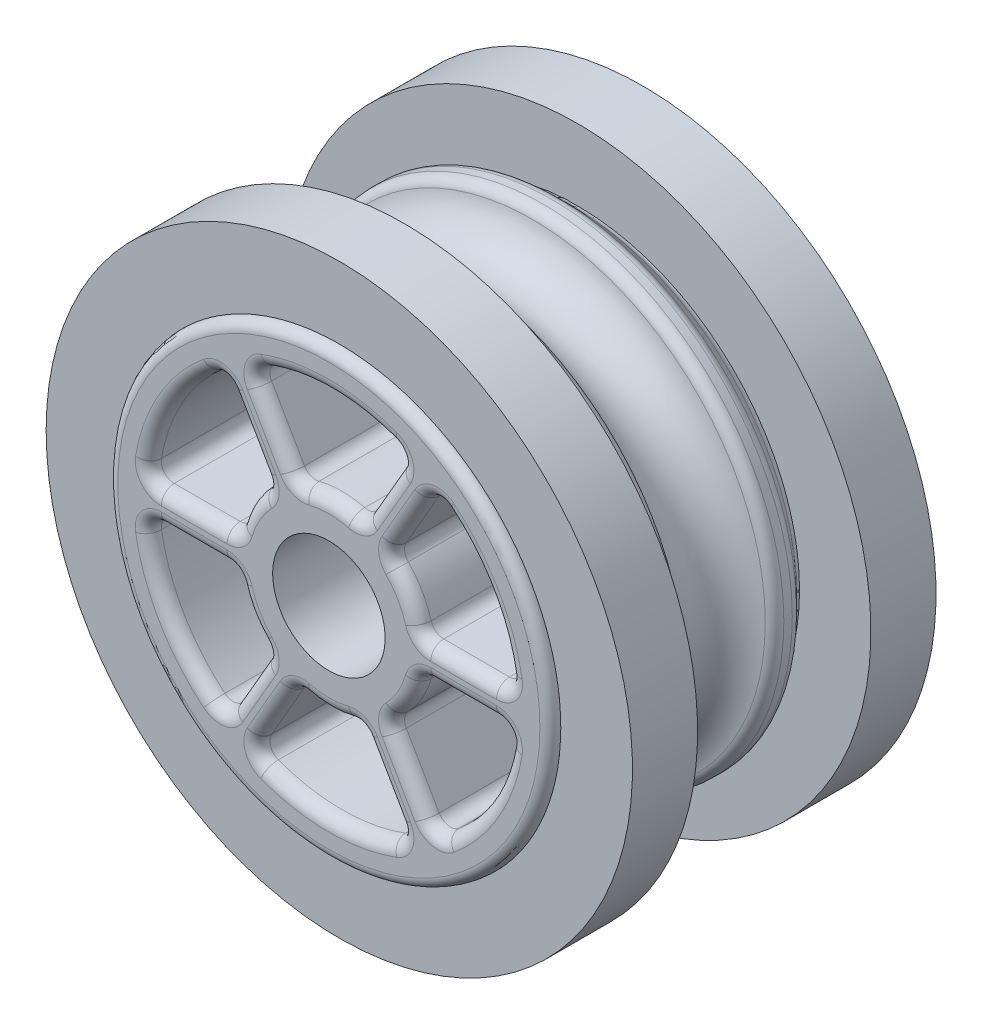
SolidWorks part; units mm, degrees
material "ABS"
ref_plane "Front Plane" through (0, 0, 0) normal (0, 0, 1) x (1, 0, 0)
ref_plane "Top Plane" through (0, 0, 0) normal (0, 1, 0) x (1, 0, 0)
ref_plane "Right Plane" through (0, 0, 0) normal (1, 0, 0) x (0, 0, -1)
sketch "Sketch1" plane through (0, 0, 0) normal (1, 0, 0) x (0, 0, -1)
  line L0 (-12.45, 4.318) -> (12.45, 4.318)
  line L1 (12.45, 4.318) -> (12.45, 17)
  line L2 (12.45, 17) -> (4.45, 17)
  line L3 (4.45, 17) -> (4.45, 18.5)
  line L4 (4.45, 18.5) -> (3.25, 18.5)
  line L5 (-3.25, 18.5) -> (-4.45, 18.5)
  line L6 (-4.45, 18.5) -> (-4.45, 17)
  line L7 (-4.45, 17) -> (-12.45, 17)
  line L8 (-12.45, 17) -> (-12.45, 4.318)
  line L9 (0, 0) -> (-26.6908, 0) construction
  arc A0 (3.25, 18.5) -> (-3.25, 18.5) centre (0, 18.5) cw
  point P0 (0, 4.318)
  point P12 (0, 0)
  point P13 (-14.9607, 4.318)
  point P15 (-26.6908, 0)
  point P19 (-14.45, 4.318)
  point P20 (0, 0)
  point P21 (0, 0)
  point P22 (-14.45, 4.318)
  dimension "D1" = 4.318
  dimension "D4" = 18.5
  dimension "D2" = 8
  dimension "D3" = 17
  dimension "D5" = 1.2
  dimension "D6" = 6.5
revolve "Revolve1" add sketch "Sketch1" angle 360 about L9
chamfer "Chamfer1" distance 2 angle 45 2 edges at (-17, 0, -4.45) (-17, 0, 4.45)
sketch "Sketch2" plane through (0, 0, 12.45) normal (0, 0, 1) x (1, 0, 0)
  line L0 (0, 0) -> (-7.625, 13.2069) construction
  line L1 (0, 0) -> (7.625, 13.2069) construction
  line L2 (-2.4688, 6.6761) -> (-5.9601, 12.7232)
  line L3 (2.4688, 6.6761) -> (5.9601, 12.7232)
  line L4 (0, 2.4) -> (-5.9601, 12.7232) construction
  line L5 (0, 2.4) -> (5.9601, 12.7232) construction
  arc A0 (-7.625, 13.2069) -> (7.625, 13.2069) centre (0, 0) cw construction
  circle A1 centre (0, 0) radius 15.25 construction
  arc A2 (-5.9601, 12.7232) -> (5.9601, 12.7232) centre (0, 0) cw
  arc A6 (2.4688, 6.6761) -> (-2.4688, 6.6761) centre (0, 0) ccw
  dimension "D1" = 60
  dimension "D2" = 1.2
extrude "Cut-Extrude1" cut sketch "Sketch2" against normal through all
pattern_circular "CirPattern1" count 6 over 360 about axis through (0, 0, 0) along (0, 0, -1) of "Cut-Extrude1"
fillet "Fillet2" radius 0.8 6 edges at (-17, 0, -6.45) (18.5, 0, -4.95) (-18.5, 0, -3.25) (-18.5, 0, 3.25) (-18.5, 0, 4.95) (17, 0, 6.45)
fillet "Fillet4" radius 0.8 2 edges at (-17, 0, -12.45) (-17, 0, 12.45)
fillet "Fillet5" radius 1 72 edges at (-4.2145, -9.6997, 12.45) (4.2145, -9.6997, 12.45) (6.2929, -8.4997, 12.45) (10.5074, -1.2, 12.45) (10.5074, 1.2, 12.45) (6.2929, 8.4997, 12.45) (4.2145, 9.6997, 12.45) (-4.2145, 9.6997, 12.45) (-6.2929, 8.4997, 12.45) (-10.5074, 1.2, 12.45) (-10.5074, -1.2, 12.45) (-6.2929, -8.4997, 12.45) (6.2929, 8.4997, -12.45) (10.5074, 1.2, -12.45) (10.5074, -1.2, -12.45) (6.2929, -8.4997, -12.45) (4.2145, -9.6997, -12.45) (-4.2145, -9.6997, -12.45) (-6.2929, -8.4997, -12.45) (-10.5074, -1.2, -12.45) (-10.5074, 1.2, -12.45) (-6.2929, 8.4997, -12.45) (-4.2145, 9.6997, -12.45) (4.2145, 9.6997, -12.45) (-5.9601, -12.7232, 0) (0, -14.05, -12.45) (5.9601, -12.7232, 0) (0, -14.05, 12.45) (8.0386, -11.5232, 0) (12.1677, -7.025, -12.45) (13.9987, -1.2, 0) (12.1677, -7.025, 12.45) (13.9987, 1.2, 0) (12.1677, 7.025, -12.45) (8.0386, 11.5232, 0) (12.1677, 7.025, 12.45) (5.9601, 12.7232, 0) (0, 14.05, -12.45) (-5.9601, 12.7232, 0) (0, 14.05, 12.45) (-8.0386, 11.5232, 0) (-12.1677, 7.025, -12.45) (-13.9987, 1.2, 0) (-12.1677, 7.025, 12.45) (-13.9987, -1.2, 0) (-12.1677, -7.025, -12.45) (-8.0386, -11.5232, 0) (-12.1677, -7.025, 12.45) (4.5473, 5.4761, 0) (7.0161, 1.2, 0) (-2.4688, 6.6761, 0) (2.4688, 6.6761, 0) (6.1644, 3.559, -12.45) (6.1644, 3.559, 12.45) (0, 7.118, -12.45) (0, 7.118, 12.45) (-7.0161, 1.2, 0) (-6.1644, 3.559, -12.45) (-4.5473, 5.4761, 0) (-6.1644, 3.559, 12.45) (-4.5473, -5.4761, 0) (-6.1644, -3.559, -12.45) (-7.0161, -1.2, 0) (-6.1644, -3.559, 12.45) (2.4688, -6.6761, 0) (0, -7.118, -12.45) (-2.4688, -6.6761, 0) (0, -7.118, 12.45) (7.0161, -1.2, 0) (6.1644, -3.559, -12.45) (4.5473, -5.4761, 0) (6.1644, -3.559, 12.45)
sketch "Sketch3" plane through (0, 0, 0) normal (1, 0, 0) x (0, 0, -1)
  line L0 (-6.7814, 17) -> (-11.65, 17) construction
  line L1 (-11.65, 17) -> (-6.65, 17)
  line L2 (-11.65, 17) -> (-11.65, 22.5)
  line L3 (-11.65, 22.5) -> (-6.65, 22.5)
  line L4 (-6.65, 17) -> (-6.65, 22.5)
  line L5 (0, 0) -> (-45.062, 0) construction
  line L6 (11.65, 17) -> (6.65, 17)
  line L7 (11.65, 17) -> (11.65, 22.5)
  line L8 (11.65, 22.5) -> (6.65, 22.5)
  line L9 (6.65, 17) -> (6.65, 22.5)
  point P4 (-9.15, 22.5)
  dimension "D1" = 5
  dimension "D2" = 22.5
revolve "Revolve2" add sketch "Sketch3" angle 360 about L5
